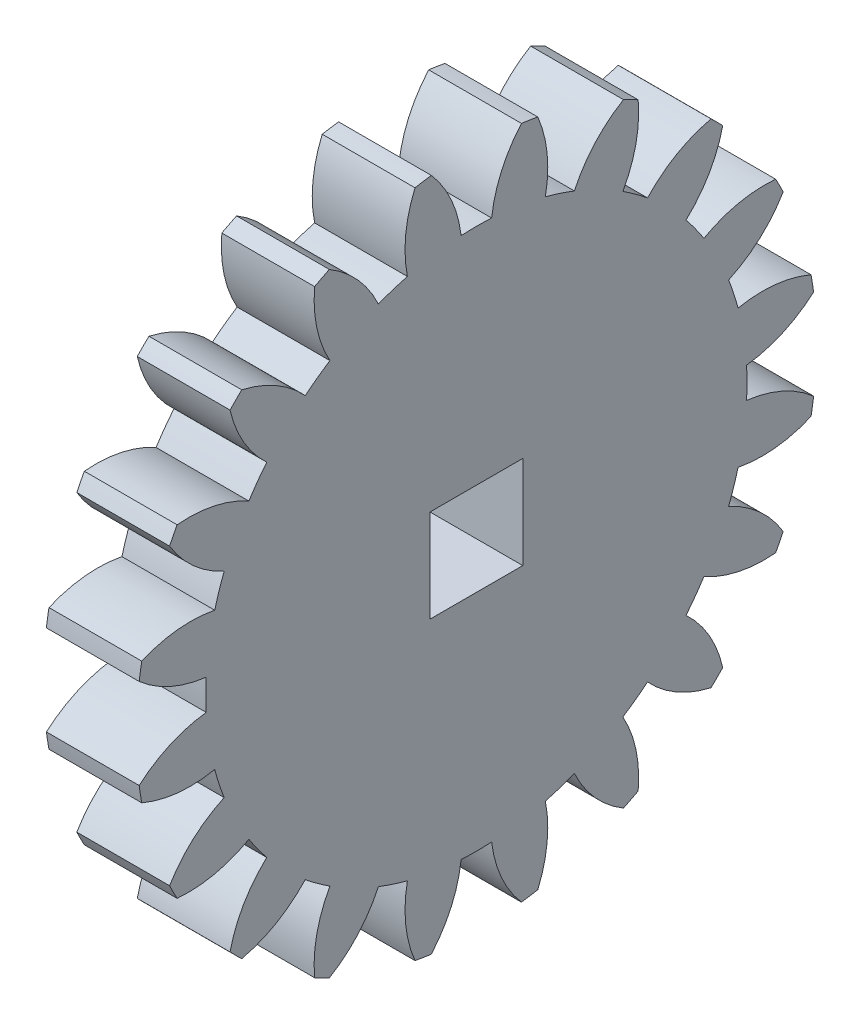
SolidWorks part; units mm, degrees
ref_plane "Plane1" through (0, 0, 0) normal (0, 0, 1) x (1, 0, 0)
ref_plane "Plane2" through (0, 0, 0) normal (0, 1, 0) x (1, 0, 0)
ref_plane "Plane3" through (0, 0, 0) normal (1, 0, 0) x (0, 0, -1)
sketch "HoldingSke" plane through (0, 0, 0) normal (0, 1, 0) x (1, 0, 0)
  line L0 (0, 0) -> (0.4698, -0.171)
  line L1 (-15, 0) -> (100, 0) construction
  line L2 (0, 0) -> (-2.1039, 2.3779)
  line L3 (0, 0) -> (-11.863, 4.5341)
  line L4 (0, 0) -> (8.1152, 2.9537)
  line L5 (0, 0) -> (-46.8476, -17.4728)
  line L6 (0, 0) -> (-4.9738, -3.3558)
  line L7 (-2.1039, 2.3779) -> (8.6586, 51.2059)
  line L8 (-76.2, 54.61) -> (-76.1, 54.61)
  line L9 (-71.009, 38.7566) -> (-53.1078, 45.2721)
  line L10 (-76.2, 71.12) -> (104.1128, 71.12)
  line L11 (0, 0) -> (-6, 0)
  line L12 (-76.2, 101.6) -> (-76.133, 101.6)
  line L13 (24.9733, 27.94) -> (52.9518, 28.4284)
  line L14 (24.9733, 27.94) -> (24.9743, 27.94)
  line L15 (24.9733, 27.94) -> (100.4006, 29.5858)
  line L16 (-63.627, -2) -> (-12.827, -2)
  circle A0 centre (0, 0) radius 0.5
  circle A1 centre (0, 0) radius 17.499
  circle A2 centre (0, 0) radius 37.5
  circle A3 centre (0, 0) radius 0.5
  dimension "MHD" = 34.998
  dimension "Hub_dia" = 75
  dimension "Bore" = 1
  dimension "MBD" = 1
  dimension "Num_teeth" = 20
  dimension "Pitch" = 0.5
  dimension "Overall_len" = 50
  dimension "Show_teeth" = 20
  dimension "Thickness" = 6
  dimension "OAL" = 50.0001
  dimension "T_dim" = 0.1
  dimension "Ap" = 20
  dimension "H" = 19.05
  dimension "Pitch_radius" = 180.3128
  dimension "Width" = 6
  dimension "Backlash" = 0.067
  dimension "Addendum_fac" = 1
  dimension "Dedendum_fac" = 1.25
  dimension "Clearance_fac" = 0.25
  dimension "Dedendum_add" = 0.001
  dimension "Module" = 2
sketch "BasProSke" plane through (0, 0, 0) normal (0, 1, 0) x (1, 0, 0)
  line L0 (-10, 0) -> (60, 0) construction
  line L1 (0, 0) -> (0, 22)
  line L2 (0, 0) -> (6, 0)
  line L3 (6, 0) -> (6, 22)
  line L4 (6, 22) -> (0, 22)
  dimension "Thickness" = 6
  dimension "Diameter" = 44
revolve "Base-Revolve" add sketch "BasProSke" angle 360 about L0
sketch "TooCutSke" plane through (0, 0, 0) normal (1, 0, 0) x (0, 0, -1)
  line L1 (0, 0) -> (0, 107) construction
  line L2 (0, 0) -> (-1.6864, 19.9288) construction
  line L3 (0, 0) -> (-6.2409, 39.4033) construction
  line L4 (-1.6864, 19.9288) -> (-3.1204, 19.7016) construction
  arc A0 (0.9862, 17.4712) -> (-0.9862, 17.4712) centre (0, 0) ccw
  arc A1 (2.9329, 21.8293) -> (-2.9329, 21.8293) centre (0, 0) ccw
  circle A2 centre (0, 0) radius 20 construction
  circle A3 centre (0, 0) radius 18.7939 construction
  arc A4 (-0.9862, 17.4712) -> (-2.9329, 21.8293) centre (-8.9313, 16.536) ccw
  arc A5 (2.9329, 21.8293) -> (0.9862, 17.4712) centre (8.9313, 16.536) ccw
  dimension "Root_dia" = 34.998
  dimension "Overcut_dia" = 44.0508
  dimension "Pitch_dia" = 40
  dimension "Base_dia" = 37.5877
  dimension "Flank_rad" = 8
  dimension "Half_ang" = 9
  dimension "Half_CT" = 1.4519
extrude "ToothCut" cut sketch "TooCutSke" along normal through all
fillet "Breaks" [suppressed] radius 0.04 tangent propagation no
fillet "RootFillets" [suppressed] radius 0.501
pattern_circular "TeethCuts" count 20 every 18 about axis through (-10, 0, 0) along (1, 0, 0) of "ToothCut", "RootFillets", "Breaks"
sketch "HubNeaOneSke" plane through (0, 0, 0) normal (-1, 0, 0) x (0, 0, 1)
  circle A0 centre (0, 0) radius 17.499
  dimension "Diameter" = 34.998
extrude "HubNearOne" [suppressed] add sketch "HubNeaOneSke" along normal blind 44.0001
sketch "HubNeaBotSke" plane through (0, 0, 0) normal (-1, 0, 0) x (0, 0, 1)
  circle A0 centre (0, 0) radius 17.499
  dimension "Diameter" = 34.998
extrude "HubNearBoth" [suppressed] add sketch "HubNeaBotSke" along normal blind 22
ref_plane "FarPln" through (6, 0, 0) normal (1, 0, 0) x (0, 0, -1)
sketch "HubFarSke" plane through (6, 0, 0) normal (1, 0, 0) x (0, 0, -1)
  circle A0 centre (0, 0) radius 17.499
  dimension "Diameter" = 34.998
extrude "HubFar" [suppressed] add sketch "HubFarSke" along normal blind 22
sketch "BorSke" plane through (0, 0, 0) normal (1, 0, 0) x (0, 0, -1)
  circle A0 centre (0, 0) radius 0.5
  dimension "Diameter" = 1
extrude "Bore" cut sketch "BorSke" along normal mid plane 100.0001
sketch "KeySke" plane through (0, 0, 0) normal (1, 0, 0) x (0, 0, -1)
  line L0 (-0.05, 0) -> (-0.05, 0.6)
  line L1 (-0.05, 0.6) -> (0.05, 0.6)
  line L2 (0.05, 0.6) -> (0.05, 0)
  line L3 (0, 0) -> (0, 34) construction
  line L4 (-0.05, 0) -> (0.05, 0)
  dimension "Offset" = 0.6
  dimension "Width" = 0.1
extrude "Keyway" [suppressed] cut sketch "KeySke" along normal mid plane 100.0001
pattern_circular "Keyway2" [suppressed] count 2 every 90 about axis through (-10, 0, 0) along (1, 0, 0)
sketch "Croquis1" plane through (6, 0, 0) normal (1, 0, 0) x (0, 0, -1)
  line L1 (0, 3) -> (-3, 3)
  line L2 (-3, 3) -> (-3, -3)
  line L3 (-3, -3) -> (3, -3)
  line L4 (3, -3) -> (3, 3)
  line L5 (3, 3) -> (0, 3)
extrude "Cortar-Extruir1" cut sketch "Croquis1" against normal blind 10
equation "' \"Module@HoldingSke\" = 6.35"
equation "' \"Num_teeth@HoldingSke\" = 12"
equation "' \"Ap@HoldingSke\" =  20"
equation "' \"Ap@HoldingSke\" = 20"
equation "' \"Width@HoldingSke\" = 0.5 * 25.4"
equation "' \"Hub_dia@HoldingSke\"= 1 * 25.4"
equation "' \"Hub_dia@HoldingSke\" = 1 * 25.4"
equation "' \"Overall_len@HoldingSke\" = 1.0 * 25.4"
equation "' \"Bore@HoldingSke\" = 0.75 * 25.4"
equation "' \"T_dim@HoldingSke\" = 0.1 * 25.4"
equation "' \"Width@KeySke\" = 0.25 * 25.4"
equation "' \"Show_teeth@HoldingSke\" = 13"
equation "' \"Backlash@HoldingSke\" = 0.009 * 25.4"
equation "' \"Addendum_fac@HoldingSke\" = 1.0"
equation "' \"Dedendum_fac@HoldingSke\" = 1.25"
equation "' \"Dedendum_add@HoldingSke\" = 0.00005 * 25.4"
equation "' \"Clearance_fac@HoldingSke\" = 0.25"
equation "\"Pitch@HoldingSke\" = 1 / \"Module@HoldingSke\""
equation "\"Overcut_dia@TooCutSke\" = (\"Num_teeth@HoldingSke\" + 2 * \"Addendum_fac@HoldingSke\") / \"Pitch@HoldingSke\" + 0.002 * 25.4"
equation "\"Pitch_dia@TooCutSke\" = \"Num_teeth@HoldingSke\" / \"Pitch@HoldingSke\""
equation "\"Base_dia@TooCutSke\" = \"Num_teeth@HoldingSke\" / \"Pitch@HoldingSke\" * cos((\"Ap@HoldingSke\"  * 3.14159265 / 180))"
equation "\"Root_dia@TooCutSke\" = (\"Num_teeth@HoldingSke\" + 2) / \"Pitch@HoldingSke\" - 2 * (\"Addendum_fac@HoldingSke\" + \"Dedendum_fac@HoldingSke\") / \"Pitch@HoldingSke\" - \"Dedendum_add@HoldingSke\" * 2"
equation "\"Half_ang@TooCutSke\" = 180 / \"Num_teeth@HoldingSke\""
equation "\"Half_CT@TooCutSke\" = \"Num_teeth@HoldingSke\" / \"Pitch@HoldingSke\" * sin((3.14159265 / 2 / \"Num_teeth@HoldingSke\")) / 2 - 7 * \"Backlash@HoldingSke\" / 4"
equation "\"Flank_rad@TooCutSke\" = \"Num_teeth@HoldingSke\" / \"Pitch@HoldingSke\" / 5"
equation "\"Radius@RootFillets\" = \"Clearance_fac@HoldingSke\" / \"Pitch@HoldingSke\" + \"Dedendum_add@HoldingSke\""
equation "\"Break_rad@Breaks\" = 0.02 / \"Pitch@HoldingSke\""
equation "\"Thickness@HoldingSke\" = \"Width@HoldingSke\""
equation "\"OAL@HoldingSke\" = \"Thickness@HoldingSke\""
equation "\"MHD@HoldingSke\" = (\"Num_teeth@HoldingSke\" + 2) / \"Pitch@HoldingSke\" - 2 * (\"Addendum_fac@HoldingSke\" + \"Dedendum_fac@HoldingSke\")  / \"Pitch@HoldingSke\" - \"Dedendum_add@HoldingSke\" * 2"
equation "\"MBD@HoldingSke\" = (\"Num_teeth@HoldingSke\" + 2) / \"Pitch@HoldingSke\" - 2 * (\"Addendum_fac@HoldingSke\" + \"Dedendum_fac@HoldingSke\")  / \"Pitch@HoldingSke\" - \"Dedendum_add@HoldingSke\" * 2 - 0.002 * 25.4"
equation "\"MHD@HoldingSke\" = ((sgn( \"MHD@HoldingSke\" - \"Hub_dia@HoldingSke\" )-1)*( \"MHD@HoldingSke\" - \"Hub_dia@HoldingSke\" ))/-2+ \"Hub_dia@HoldingSke\""
equation "\"MBD@HoldingSke\" = ((sgn( \"MBD@HoldingSke\" - \"Bore@HoldingSke\" )-1)*( \"MBD@HoldingSke\" - \"Bore@HoldingSke\" ))/-2+ \"Bore@HoldingSke\""
equation "\"OAL@HoldingSke\" = ((sgn( \"OAL@HoldingSke\" - \"Overall_len@HoldingSke\" )+1)*( \"OAL@HoldingSke\" - \"Overall_len@HoldingSke\" ))/2 + \"Overall_len@HoldingSke\" + 0.000002 * 25.4"
equation "\"Num_teeth@TeethCuts\" = int( \"Show_teeth@HoldingSke\" ) + 1"
equation "\"Num_teeth@TeethCuts\" = ((sgn( \"Num_teeth@TeethCuts\" - \"Num_teeth@HoldingSke\" )-1)*( \"Num_teeth@TeethCuts\" - \"Num_teeth@HoldingSke\" ))/-2+ \"Num_teeth@HoldingSke\""
equation "\"Num_teeth@TeethCuts\" = ((sgn( \"Num_teeth@TeethCuts\" - 2.0)+1)*( \"Num_teeth@TeethCuts\" - 2.0))/2 +2.0"
equation "\"Angle@TeethCuts\" = 360.0 / \"Num_teeth@HoldingSke\""
equation "\"Diameter@BasProSke\" = (\"Num_teeth@HoldingSke\" + 2 * \"Addendum_fac@HoldingSke\") / \"Pitch@HoldingSke\""
equation "\"Thickness@BasProSke\"  = \"Thickness@HoldingSke\""
equation "' \"Fillet_rad@BasProSke\" =  \"Thickness@HoldingSke\" * 0.05"
equation "' \"Fillet_rad@BasProSke\" = \"Thickness@HoldingSke\" * 0.05"
equation "\"MHD@HoldingSke\" = ((sgn( \"MHD@HoldingSke\" - \"Root_dia@TooCutSke\" )-1)*( \"MHD@HoldingSke\" - \"Root_dia@TooCutSke\" ))/-2+ \"Root_dia@TooCutSke\""
equation "\"Diameter@HubNeaOneSke\" = \"MHD@HoldingSke\""
equation "\"Length@HubNearOne\" = \"OAL@HoldingSke\" - \"Thickness@BasProSke\""
equation "\"Diameter@HubNeaBotSke\" = \"MHD@HoldingSke\""
equation "\"Length@HubNearBoth\" = ( \"OAL@HoldingSke\" - \"Thickness@BasProSke\" ) / 2.0"
equation "\"Thickness@FarPln\" = \"Thickness@BasProSke\""
equation "\"Diameter@HubFarSke\" = \"MHD@HoldingSke\""
equation "\"Length@HubFar\" = ( \"OAL@HoldingSke\" - \"Thickness@BasProSke\" ) / 2.0"
equation "\"Diameter@BorSke\" = \"MBD@HoldingSke\""
equation "\"D1@Bore\" = \"OAL@HoldingSke\" * 2.0"
equation "\"D1@Keyway\" = \"OAL@HoldingSke\" * 2.0"
equation "\"Offset@KeySke\" = \"T_dim@HoldingSke\" + \"MBD@HoldingSke\" / 2.0"
